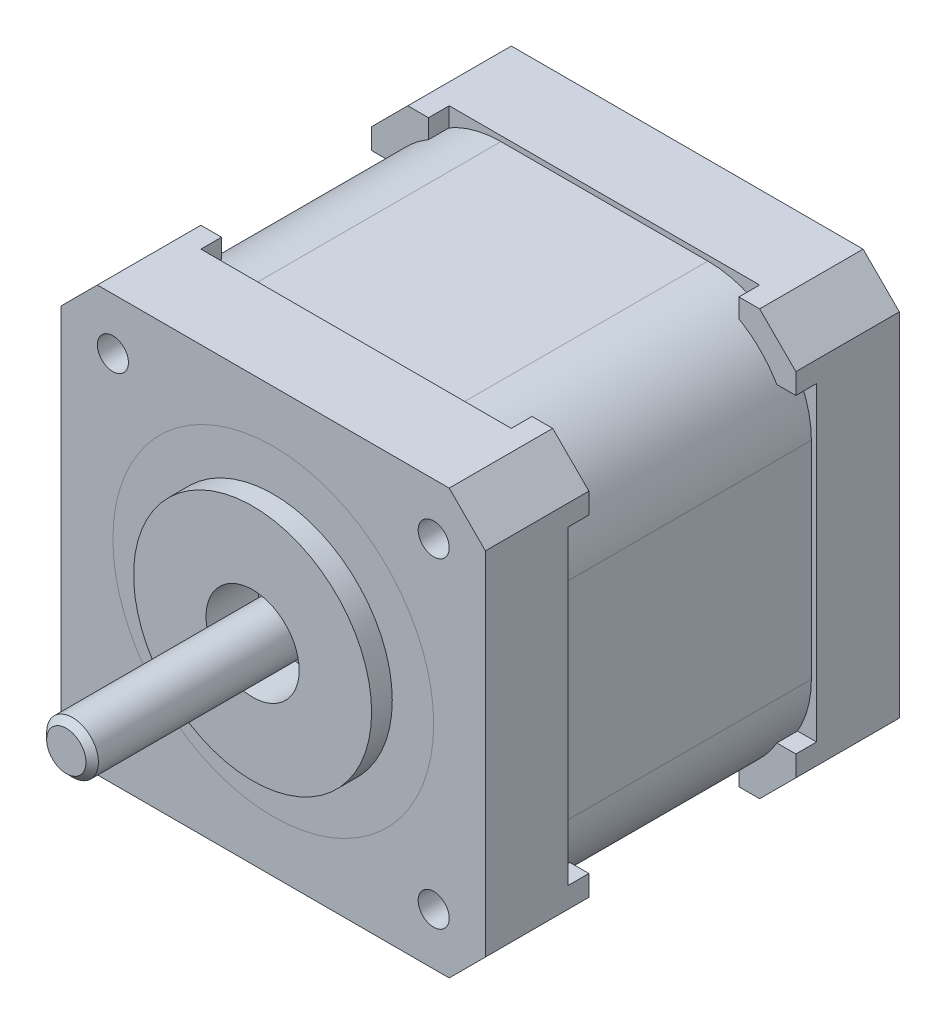
SolidWorks part; units mm, degrees
ref_plane "Alzado" through (0, 0, 0) normal (0, 0, 1) x (1, 0, 0)
ref_plane "Planta" through (0, 0, 0) normal (0, 1, 0) x (1, 0, 0)
ref_plane "Vista lateral" through (0, 0, 0) normal (1, 0, 0) x (0, 0, -1)
sketch "Croquis1" plane through (0, 0, 0) normal (0, 0, 1) x (1, 0, 0)
  line L2 (0, 15) -> (-15, 15) construction
  line L3 (-15, -15) -> (-15, 15) construction
  line L4 (-17, 20.5) -> (-20.5, 17)
  line L5 (15, -15) -> (15, 15) construction
  line L6 (0, 20.5) -> (0, -20.5) construction
  line L7 (-20.5, 0) -> (20.5, 0) construction
  line L8 (20.5, 17) -> (20.5, -17)
  line L9 (17, 20.5) -> (20.5, 17)
  line L10 (0, -15) -> (-15, -15) construction
  line L11 (17, -20.5) -> (-17, -20.5)
  line L12 (17, -20.5) -> (20.5, -17)
  line L13 (-17, -20.5) -> (-20.5, -17)
  line L16 (17, 20.5) -> (-17, 20.5)
  line L18 (-20.5, 17) -> (-20.5, -17)
  circle A0 centre (-15, 15) radius 3
  circle A1 centre (15, 15) radius 3
  circle A2 centre (15, -15) radius 3
  circle A3 centre (-15, -15) radius 3
  point P1 (-20.5, 20.5)
  point P3 (-20.5, 20.5)
  point P5 (0, 16.1111)
  point P7 (-20.5, 18)
  point P9 (0, 0)
  point P10 (-20.5, 21.0798)
  point P12 (-23.9805, 17)
  point P23 (20.5, 20.5)
  point P25 (0, 0)
  point P26 (15, 0)
  point P27 (-15, 0)
  point P34 (20.5, -20.5)
  point P35 (-20.5, -20.5)
  dimension "D4" = 6
  dimension "D2" = 30
  dimension "D3" = 15
  dimension "D1" = 41
extrude "Saliente-Extruir1" add sketch "Croquis1" along normal mid plane 40 contours L16 L4 L18 L13 L11 L12 L8 L9
sketch "Croquis2" plane through (0, 0, 20) normal (0, 0, 1) x (1, 0, 0)
  line L0 (20.5, -15) -> (-20.5, -15)
  line L1 (20.5, -15) -> (20.5, 15)
  line L2 (-20.5, -15) -> (-20.5, 15)
  line L3 (20.5, 15) -> (-20.5, 15)
  line L4 (20.5, -15) -> (-20.5, 15) construction
  line L5 (-20.5, -15) -> (20.5, 15) construction
  line L6 (-20.5, 17) -> (-20.5, -17) construction
  line L7 (17, 20.5) -> (-17, 20.5) construction
  line L8 (15, -20.5) -> (-15, -20.5)
  line L9 (15, -20.5) -> (15, 20.5)
  line L10 (15, 20.5) -> (-15, 20.5)
  line L11 (-15, -20.5) -> (-15, 20.5)
  line L12 (15, -20.5) -> (-15, 20.5) construction
  line L13 (15, 20.5) -> (-15, -20.5) construction
  point P1 (0, 0)
  point P3 (0, 0)
  line M10 (17, 20.5) -> (-17, 20.5)
  line M12 (-20.5, 17) -> (-20.5, -17)
  line M14 (-17, -20.5) -> (17, -20.5)
  line M16 (20.5, -17) -> (20.5, 17)
  dimension "D1" = 30
extrude "Cortar-Extruir1" cut sketch "Croquis2" against normal offset from surface (24 mm away) 8 from offset 8 contours L11 L3 L9 M10 | L11 L0 L9 L3 | L9 L0 L3 M16 | L11 L9 L0 M14 | L0 L11 L3 M12 region at (17.75, 0, 20) region at (0, -17.75, 20) region at (0, 0, 20) region at (-17.75, 0, 20) region at (0, 17.75, 20) up to face at (0, 0, -20) offset against normal yes
sketch "Croquis3" plane through (0, 0, -20) normal (0, 0, -1) x (-1, 0, 0)
  line L8 (-17, 20.5) -> (-20.5, 17)
  line L9 (-20.5, 17) -> (-20.5, -17)
  line L10 (-20.5, -17) -> (-17, -20.5)
  line L11 (-17, -20.5) -> (17, -20.5)
  line L12 (17, -20.5) -> (20.5, -17)
  line L13 (20.5, -17) -> (20.5, 17)
  line L14 (20.5, 17) -> (17, 20.5)
  line L15 (17, 20.5) -> (-17, 20.5)
  line L16 (-17, 20.5) -> (-20.5, 17)
  line L17 (-20.5, 17) -> (-20.5, -17)
  line L18 (-20.5, -17) -> (-17, -20.5)
  line L19 (-17, -20.5) -> (17, -20.5)
  line L20 (17, -20.5) -> (20.5, -17)
  line L21 (20.5, -17) -> (20.5, 17)
  line L22 (20.5, 17) -> (17, 20.5)
  line L23 (17, 20.5) -> (-17, 20.5)
  dimension "D1" = 0
extrude "Cortar-Extruir2" cut sketch "Croquis3" against normal offset from surface (20 mm away) 10 from offset 10 up to face at (0, 0, 20) offset against normal yes
sketch "Croquis4" plane through (0, 0, 20) normal (0, 0, 1) x (1, 0, 0)
  line L2 (-20, 10) -> (-20, -10)
  line L3 (10, 20) -> (-10, 20)
  line L4 (17, 20.5) -> (-17, 20.5) construction
  line L5 (-20.5, 17) -> (-20.5, -17) construction
  line L6 (0, -1000) -> (0, 49000) construction
  line L7 (-1000, 0) -> (49000, 0) construction
  line L8 (20, 10) -> (20, -10)
  line L9 (10, -20) -> (-10, -20)
  arc A4 (-10, 20) -> (-20, 10) centre (-10, 10) ccw
  arc A5 (10, 20) -> (20, 10) centre (10, 10) cw
  arc A6 (10, -20) -> (20, -10) centre (10, -10) ccw
  arc A7 (-10, -20) -> (-20, -10) centre (-10, -10) cw
  dimension "D1" = 10
  dimension "D3" = 0.5
  dimension "D4" = 0.5
extrude "Cortar-Extruir3" cut sketch "Croquis4<4>" against normal up to surface (32 mm away) from surface up to face at (0, 0, -12) starting at face at (0, 0, 12)
sketch "Croquis4<4>" plane through (0, 0, 20) normal (0, 0, 1) x (1, 0, 0) same geometry as "Croquis4"
extrude "Saliente-Extruir2" add sketch "Croquis4" against normal up to next from surface separate body contours A5 L8 A6 L9 A7 L2 A4 L3 starting at face at (0, 0, 12)
sketch "Croquis5" plane through (0, 0, 20) normal (0, 0, 1) x (1, 0, 0)
  circle A0 centre (0, 0) radius 15.5
  circle A1 centre (0, 0) radius 11.5
  circle A2 centre (0, 0) radius 4.5
  circle A3 centre (0, 0) radius 2.5
  point P7 (0, 0)
  dimension "D1" = 31
  dimension "D2" = 23
  dimension "D3" = 9
  dimension "D4" = 5
extrude "Cortar-Extruir4" cut sketch "Croquis5" against normal blind 3 contours A0 A1 | A1 A2 | A2 A3 | A3 region at (-15.0616, 0, 20) region at (-11.1747, 0, 20) region at (-4.3727, 0, 20) region at (0, 0, 20)
extrude "Saliente-Extruir3" add sketch "Croquis5<3>" against normal up to body separate body contours A0 A1 region at (-15.0616, 0, 20)
sketch "Croquis5<3>" plane through (0, 0, 20) normal (0, 0, 1) x (1, 0, 0) same geometry as "Croquis5"
extrude "Saliente-Extruir4" add sketch "Croquis5<4>" along normal blind 5 from surface separate body contours A1 A2 region at (-11.1747, 0, 20) starting at face at (15.5, 0, 17)
sketch "Croquis5<4>" plane through (0, 0, 20) normal (0, 0, 1) x (1, 0, 0) same geometry as "Croquis5"
extrude "Saliente-Extruir5" add sketch "Croquis5<5>" along normal blind 23 from surface contours A3 region at (0, 0, 20) starting at face at (15.5, 0, 17)
sketch "Croquis5<5>" plane through (0, 0, 20) normal (0, 0, 1) x (1, 0, 0) same geometry as "Croquis5"
chamfer "Chaflán1" distance 0.6 angle 45 1 edges at (2.5, 0, 40)
sketch "Croquis6" plane through (0, 0, 20) normal (0, 0, 1) x (1, 0, 0)
  line L0 (15.5, -15.5) -> (15.5, 15.5) construction
  line L1 (15.5, -15.5) -> (-15.5, -15.5) construction
  line L2 (15.5, 15.5) -> (-15.5, 15.5) construction
  line L3 (-15.5, -15.5) -> (-15.5, 15.5) construction
  line L4 (15.5, -15.5) -> (-15.5, 15.5) construction
  line L5 (15.5, 15.5) -> (-15.5, -15.5) construction
  circle A0 centre (-15.5, 15.5) radius 1.5
  circle A1 centre (15.5, -15.5) radius 1.5
  circle A2 centre (15.5, 15.5) radius 1.5
  circle A3 centre (-15.5, -15.5) radius 1.5
  point P3 (0, 0)
  dimension "D2" = 3
  dimension "D1" = 31
extrude "Cortar-Extruir5" cut sketch "Croquis6" against normal blind 6 contours A3 | A1 | A2 | A0 region at (15.5, -15.5, 20) region at (15.5, 15.5, 20) region at (-15.5, -15.5, 20)
